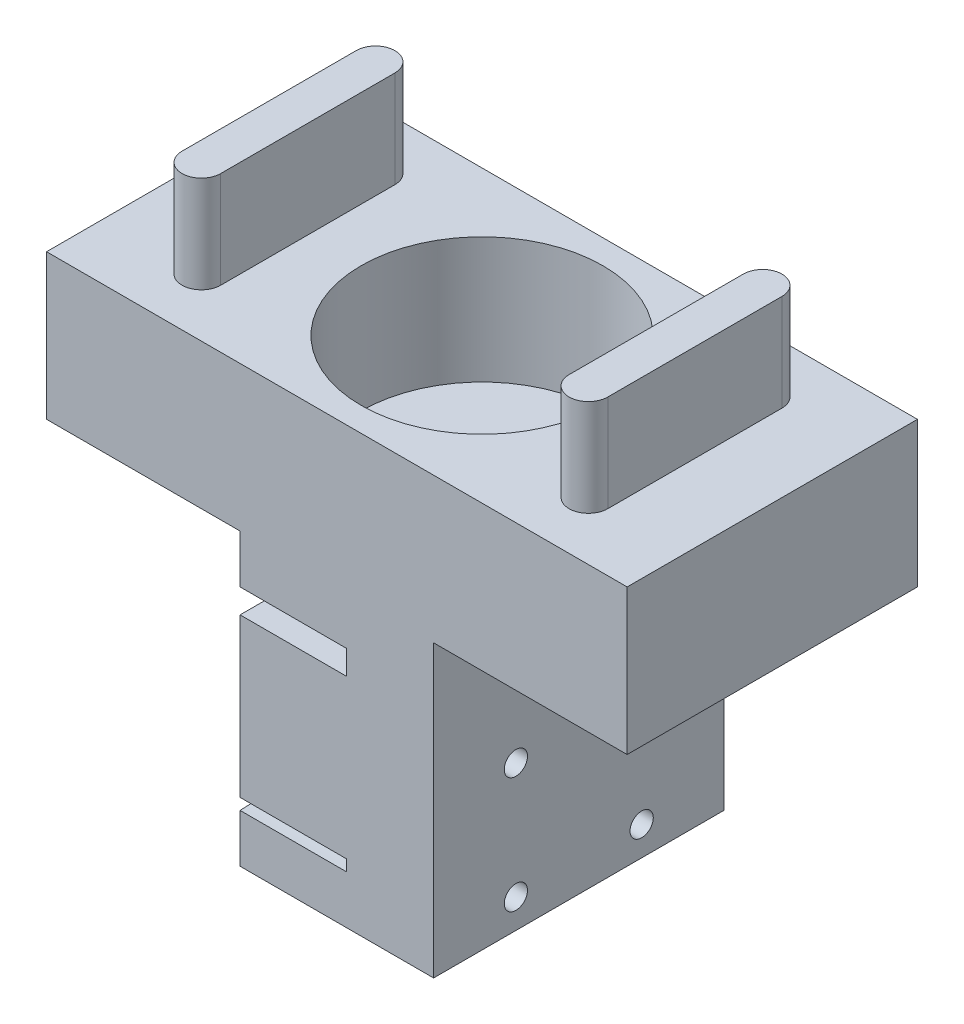
SolidWorks part; units mm, degrees
ref_plane "前视基准面" through (0, 0, 0) normal (0, 0, 1) x (1, 0, 0)
ref_plane "上视基准面" through (0, 0, 0) normal (0, 1, 0) x (1, 0, 0)
ref_plane "右视基准面" through (0, 0, 0) normal (1, 0, 0) x (0, 0, -1)
sketch "草图1" plane through (0, 0, 0) normal (0, 0, 1) x (1, 0, 0)
  line L1 (0, 0) -> (20, 0)
  line L2 (0, 0) -> (0, 30)
  line L3 (0, 30) -> (20, 30)
  line L4 (20, 0) -> (20, 30)
  dimension "D1" = 20
  dimension "D2" = 30
extrude "凸台-拉伸1" add sketch "草图1" along normal blind 30
sketch "草图3" plane through (0, 0, 0) normal (-1, 0, 0) x (0, 0, 1)
  line L0 (15, 29.8831) -> (15, 0.3212) construction
  line L1 (30, 0) -> (0, 0) construction
  line L2 (0.4, 6.1666) -> (0.3937, 6.4165)
  line L4 (0, 22) -> (0.3937, 6.4165) construction
  line L6 (0, 30) -> (0, 0) construction
  line L8 (1.5904, 6.4929) -> (0, 22) construction
  line L9 (14.0438, 15.2345) -> (0, 22) construction
  line L13 (14.0438, 15.2345) -> (14.0438, 16.1453)
  line L21 (14.0438, 16.1453) -> (15.9562, 16.1453)
  line L23 (1.5904, 6.4929) -> (1.6159, 6.2442)
  line L24 (2.2589, 4.3732) -> (0, 22) construction
  line L26 (3.6055, 6.5774) -> (3.5486, 6.8208)
  line L27 (2.3713, 6.593) -> (2.4094, 6.3459)
  line L28 (4.4666, 4.8591) -> (0, 22) construction
  line L30 (7.378, 7.985) -> (7.2616, 8.2062)
  line L31 (6.1798, 7.6888) -> (6.2789, 7.4593)
  line L32 (5.4493, 7.395) -> (5.5367, 7.1608)
  line L33 (4.3797, 6.7791) -> (4.3105, 7.0194)
  line L34 (8.6606, 6.5108) -> (-0.0001, 22.0002) construction
  line L36 (8.0763, 8.3754) -> (7.9488, 8.5904)
  line L37 (8.956, 9.2411) -> (9.0997, 9.0365)
  line L38 (9.5889, 9.7096) -> (9.7426, 9.5125)
  line L39 (10.6737, 10.2983) -> (10.5052, 10.483)
  line L40 (11.2509, 10.8522) -> (11.0733, 11.0282)
  line L41 (11.8839, 11.9118) -> (12.0745, 11.75)
  line L42 (12.3782, 12.5247) -> (12.5767, 12.3728)
  line L43 (13.2795, 13.368) -> (13.0699, 13.5042)
  line L44 (15.2666, 12.6161) -> (0, 22) construction
  line L46 (30, 30) -> (30, 0) construction
  line L47 (0, 6.1615) -> (0, 5)
  line L49 (13.6984, 14.0495) -> (13.4822, 14.175)
  line L50 (30, 6.1615) -> (30, 5)
  line L51 (29.6, 6.1666) -> (29.6063, 6.4165)
  line L52 (28.4096, 6.4929) -> (28.3841, 6.2442)
  line L53 (27.6287, 6.593) -> (27.5906, 6.3459)
  line L54 (26.3945, 6.5774) -> (26.4514, 6.8208)
  line L55 (25.6203, 6.7791) -> (25.6895, 7.0194)
  line L56 (24.5507, 7.395) -> (24.4633, 7.1608)
  line L57 (23.8202, 7.6888) -> (23.7211, 7.4593)
  line L58 (22.622, 7.985) -> (22.7384, 8.2062)
  line L59 (21.9237, 8.3754) -> (22.0512, 8.5904)
  line L60 (21.044, 9.2411) -> (20.9003, 9.0365)
  line L61 (20.4111, 9.7096) -> (20.2574, 9.5125)
  line L62 (19.3263, 10.2983) -> (19.4948, 10.483)
  line L63 (18.7491, 10.8522) -> (18.9267, 11.0282)
  line L64 (18.1161, 11.9118) -> (17.9255, 11.75)
  line L65 (17.6218, 12.5247) -> (17.4233, 12.3728)
  line L66 (16.7205, 13.368) -> (16.9301, 13.5042)
  line L67 (16.3016, 14.0495) -> (16.5178, 14.175)
  line L69 (15.9562, 16.1453) -> (15.9562, 15.2345)
  arc A24 (0, 5) -> (15, 14) centre (0, 22) ccw
  arc A27 (0, 7) -> (15, 22) centre (0, 22) ccw construction
  arc A28 (0, 6.1615) -> (0.4, 6.1666) centre (0, 22) ccw
  arc A29 (0.3937, 6.4165) -> (1.5904, 6.4929) centre (0.9935, 6.4317) cw
  arc A30 (0, 6.4115) -> (15, 17.7574) centre (0, 22) ccw construction
  arc A31 (1.6159, 6.2442) -> (2.4094, 6.3459) centre (0, 22) ccw
  arc A32 (4.3797, 6.7791) -> (3.6055, 6.5774) centre (0, 22) cw
  arc A33 (3.5486, 6.8208) -> (2.3713, 6.593) centre (2.9644, 6.6842) ccw
  arc A34 (8.0763, 8.3754) -> (7.378, 7.985) centre (0, 22) cw
  arc A35 (7.2616, 8.2062) -> (6.1798, 7.6888) centre (6.7306, 7.9267) ccw
  arc A36 (6.2789, 7.4593) -> (5.5367, 7.1608) centre (0, 22) cw
  arc A37 (4.3105, 7.0194) -> (5.4493, 7.395) centre (4.8871, 7.1853) cw
  arc A38 (7.9488, 8.5904) -> (8.956, 9.2411) centre (8.4649, 8.8964) cw
  arc A39 (9.0997, 9.0365) -> (9.7426, 9.5125) centre (0, 22) ccw
  arc A40 (10.5052, 10.483) -> (9.5889, 9.7096) centre (10.0619, 10.0787) ccw
  arc A41 (10.6737, 10.2983) -> (11.2509, 10.8522) centre (0, 22) ccw
  arc A42 (11.0733, 11.0282) -> (11.8839, 11.9118) centre (11.4956, 11.4544) cw
  arc A43 (12.5767, 12.3728) -> (12.0745, 11.75) centre (0, 22) cw
  arc A44 (13.0699, 13.5042) -> (12.3782, 12.5247) centre (12.7429, 13.0012) ccw
  arc A45 (13.6984, 14.0495) -> (13.2795, 13.368) centre (0, 22) cw
  arc A46 (30, 5) -> (15, 14) centre (30, 22) cw
  arc A47 (30, 6.1615) -> (29.6, 6.1666) centre (30, 22) cw
  arc A48 (29.6063, 6.4165) -> (28.4096, 6.4929) centre (29.0065, 6.4317) ccw
  arc A49 (13.4822, 14.175) -> (14.0438, 15.2345) centre (13.7834, 14.6939) cw
  arc A50 (28.3841, 6.2442) -> (27.5906, 6.3459) centre (30, 22) cw
  arc A51 (26.4514, 6.8208) -> (27.6287, 6.593) centre (27.0356, 6.6842) cw
  arc A52 (25.6203, 6.7791) -> (26.3945, 6.5774) centre (30, 22) ccw
  arc A53 (25.6895, 7.0194) -> (24.5507, 7.395) centre (25.1129, 7.1853) ccw
  arc A54 (23.7211, 7.4593) -> (24.4633, 7.1608) centre (30, 22) ccw
  arc A55 (22.7384, 8.2062) -> (23.8202, 7.6888) centre (23.2694, 7.9267) cw
  arc A56 (21.9237, 8.3754) -> (22.622, 7.985) centre (30, 22) ccw
  arc A57 (22.0512, 8.5904) -> (21.044, 9.2411) centre (21.5351, 8.8964) ccw
  arc A58 (20.9003, 9.0365) -> (20.2574, 9.5125) centre (30, 22) cw
  arc A59 (19.4948, 10.483) -> (20.4111, 9.7096) centre (19.9381, 10.0787) cw
  arc A60 (19.3263, 10.2983) -> (18.7491, 10.8522) centre (30, 22) cw
  arc A61 (18.9267, 11.0282) -> (18.1161, 11.9118) centre (18.5044, 11.4544) ccw
  arc A62 (17.4233, 12.3728) -> (17.9255, 11.75) centre (30, 22) ccw
  arc A63 (16.9301, 13.5042) -> (17.6218, 12.5247) centre (17.2571, 13.0012) cw
  arc A64 (16.3016, 14.0495) -> (16.7205, 13.368) centre (30, 22) ccw
  arc A65 (16.5178, 14.175) -> (15.9562, 15.2345) centre (16.2166, 14.6939) ccw
  dimension "D1" = 0.8
  dimension "D2" = 17
  dimension "D4" = 0.4
  dimension "D6" = 0.6
  dimension "D8" = 15
  dimension "D9" = 0.8
  dimension "D3" = 22
  dimension "D5" = 0.25
  dimension "D7" = 0.25
  dimension "D10" = 0.8
  dimension "D11" = 0.8
extrude "切除-拉伸1" cut sketch "草图3" against normal blind 11
sketch "草图5" plane through (0, 0, 0) normal (-1, 0, 0) x (0, 0, 1)
  line L0 (15, 15.3094) -> (15, 31.009) construction
  line L1 (12, 21) -> (12, 11.0347)
  line L2 (30, 30) -> (0, 30) construction
  line L4 (12, 11.0347) -> (15, 15.3094)
  line L5 (12, 21) -> (18, 21)
  line L6 (18, 11.0347) -> (15, 15.3094)
  line L7 (18, 21) -> (18, 11.0347)
  line L8 (0, 30) -> (0, 6.1615) construction
  line L9 (0, 25) -> (30, 25)
  line L10 (0, 25) -> (0, 22.5)
  line L11 (0, 22.5) -> (30, 22.5)
  line L12 (30, 25) -> (30, 22.5)
  line L13 (30, 30) -> (30, 6.1615) construction
  dimension "D1" = 6
  dimension "D2" = 9
  dimension "D3" = 5
  dimension "D4" = 2.5
extrude "切除-拉伸2" cut sketch "草图5" against normal blind 11
hole_wizard "M2 间隙孔1" positions "草图7" profile "草图8" hole size "M2" standard "ISO" end condition through all
sketch "草图7" plane through (0, 0, 0) normal (-1, 0, 0) x (0, 0, 1)
  line L0 (15, 28.8657) -> (15, -1.1343) construction
  line L3 (30, 0) -> (0, 0) construction
  line L4 (0, 30) -> (0, 25) construction
  line L5 (30, 30) -> (30, 25) construction
  point P12 (8.5, 3)
  point P14 (8.5, 15)
  point P29 (21.5, 3)
  point P30 (21.5, 15)
  dimension "D1" = 6.5
  dimension "D2" = 12
  dimension "D3" = 0
  dimension "D4" = 3
sketch "草图8" plane through (0, 15, 21.5) normal (0, 1, 0) x (0, 0, 1)
  line L0 (0, 0) -> (0, 20)
  line L1 (0, 20) -> (1.2, 20)
  line L2 (1.2, 20) -> (1.2, 0.025)
  line L3 (1.2, 0.025) -> (1.225, 0)
  line L5 (1.225, 0) -> (0, 0)
  line L6 (-1.2, 0.025) -> (-1.225, 0) construction
  line L11 (0, -6.35) -> (0, 107.95) construction
  dimension "通孔孔直径" = 2.4
  dimension "通孔孔深度" = 20
  dimension "近端锥形沉头孔直径" = 2.45
  dimension "近端锥形沉头孔角度" = 90
sketch "草图9" plane through (0, 0, 0) normal (-1, 0, 0) x (0, 0, 1)
  circle A0 centre (8.5, 15) radius 2.5
  circle A1 centre (8.5, 3) radius 2.5
  circle A2 centre (21.5, 15) radius 2.5
  circle A3 centre (21.5, 3) radius 2.5
  circle A4 centre (21.5, 3) radius 1.225 construction
  dimension "D1" = 5
  dimension "D2" = 5
  dimension "D3" = 5
  dimension "D4" = 5
extrude "切除-拉伸3" cut sketch "草图9" against normal blind 10
sketch "草图10" plane through (0, 30, 0) normal (0, 1, 0) x (1, 0, 0)
  line L0 (20, -30) -> (0, -30) construction
  line L1 (-20, 0) -> (40, 0)
  line L2 (-20, 0) -> (-20, -30)
  line L3 (-20, -30) -> (40, -30)
  line L4 (40, 0) -> (40, -30)
  line L5 (0, -30) -> (0, 0) construction
  line L7 (20, 0) -> (0, 0) construction
  dimension "D1" = 0
  dimension "D2" = 60
  dimension "D3" = 20
  dimension "D4" = 0
extrude "凸台-拉伸2" add sketch "草图10" along normal blind 15
sketch "草图11" plane through (0, 45, 0) normal (0, 1, 0) x (1, 0, 0)
  line L0 (10, 0) -> (10, -30) construction
  line L4 (-20, 0) -> (-20, -30)
  line L5 (-20, -30) -> (40, -30)
  line L6 (40, -30) -> (40, 0)
  line L7 (40, 0) -> (-20, 0)
  line L8 (-20, 0) -> (-20, -30)
  line L9 (-20, -30) -> (40, -30)
  line L10 (40, -30) -> (40, 0)
  line L11 (40, 0) -> (-20, 0)
  circle A0 centre (10, -15) radius 12.5
  dimension "D2" = 25
  dimension "D1" = 0
extrude "切除-拉伸4" cut sketch "草图11" against normal blind 13 contours L0 A0 | A0 L0 region at (15.3052, 45, 15) region at (4.6948, 45, 15)
sketch "草图12" plane through (0, 45, 0) normal (0, 1, 0) x (1, 0, 0)
  line L0 (10, 0) -> (10, -30) construction
  line L1 (40, 0) -> (-20, 0) construction
  line L2 (-20, -30) -> (40, -30) construction
  line L3 (-20, -15) -> (26.246, -15) construction
  line L5 (-12, -6) -> (-12, -24)
  line L7 (-8, -6) -> (-8, -24)
  line L8 (-20, 0) -> (-20, -30) construction
  line L9 (28, -6) -> (28, -24)
  line L10 (32, -6) -> (32, -24)
  arc A0 (-12, -6) -> (-8, -6) centre (-10, -6) cw
  arc A1 (-12, -24) -> (-8, -24) centre (-10, -24) ccw
  arc A2 (32, -24) -> (28, -24) centre (30, -24) cw
  arc A3 (32, -6) -> (28, -6) centre (30, -6) ccw
  dimension "D4" = 2
  dimension "D1" = 18
  dimension "D2" = 9
  dimension "D3" = 8
extrude "凸台-拉伸4" add sketch "草图12" along normal blind 10
